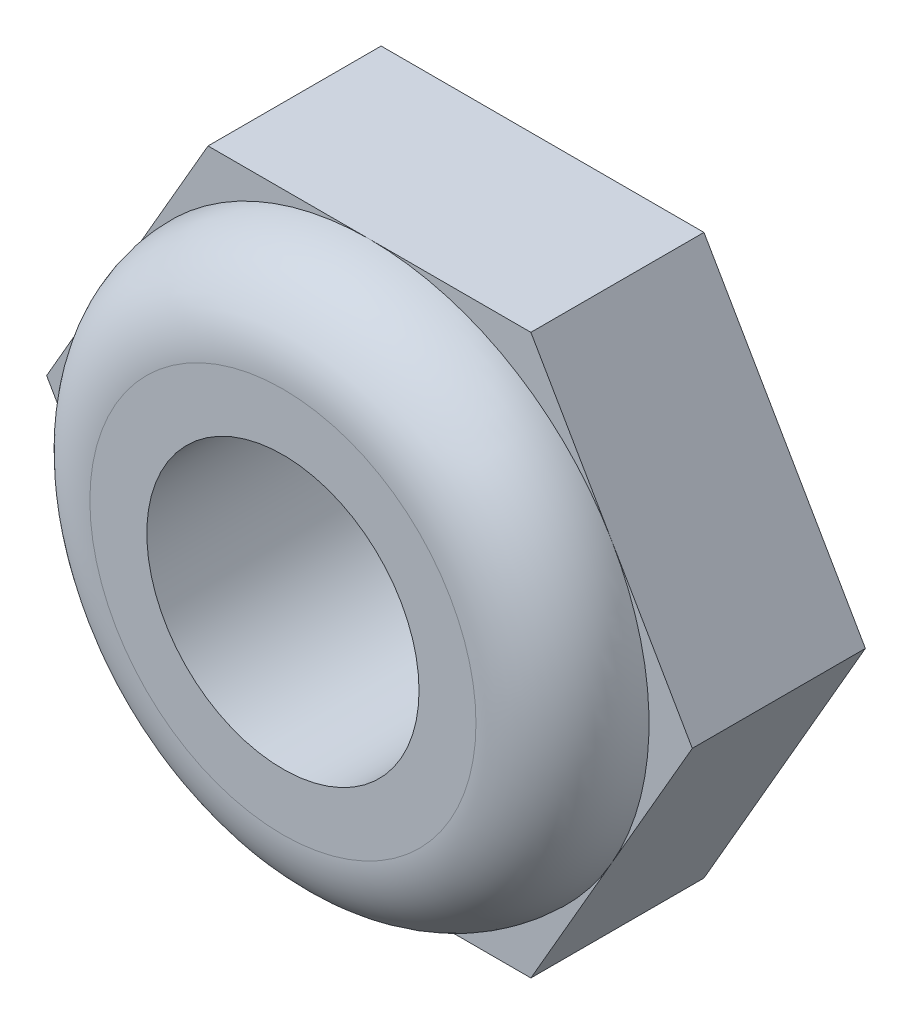
SolidWorks part; units mm, degrees
material "Alloy Steel"
ref_plane "Plane1" through (0, 0, 0) normal (0, 0, 1) x (1, 0, 0)
ref_plane "Plane2" through (0, 0, 0) normal (0, 1, 0) x (1, 0, 0)
ref_plane "Plane3" through (0, 0, 0) normal (1, 0, 0) x (0, 0, -1)
ref_axis "Axis1" through (-83.9706, 0, 0) along (1, 0, 0)
ref_axis "Axis2" through (0, 0, -0.258) along (0, 0, 1)
ref_axis "Axis3" through (0, 6.1119, 0) along (0, -1, 0)
sketch "Sketch1" plane through (0, 0, 0) normal (0, 0, 1) x (1, 0, 0)
  line L1 (3.2079, 5.5562) -> (-3.2079, 5.5562)
  line L2 (-3.2079, 5.5562) -> (-6.4158, 0)
  line L3 (-6.4158, 0) -> (-3.2079, -5.5563)
  line L4 (-3.2079, -5.5563) -> (3.2079, -5.5562)
  line L5 (3.2079, -5.5562) -> (6.4158, 0)
  line L6 (6.4158, 0) -> (3.2079, 5.5562)
  circle A0 centre (0, 0) radius 5.5562 construction
  circle A1 centre (0, 0) radius 2.7051
  dimension "D1" = 11.1125
  dimension "D2" = 5.4102
extrude "Boss-Extrude1" add sketch "Sketch1" along normal blind 5.1594
sketch "Sketch2" plane through (0, 0, 0) normal (1, 0, 0) x (0, 0, -1)
  line L0 (-3.4396, 5.5562) -> (-5.1594, 5.5562) construction
  line L1 (-5.1594, 5.5562) -> (0, 5.5562) construction
  line L2 (-5.1594, 5.5562) -> (-5.1594, 3.8365)
  line L3 (-5.1594, 0) -> (-5.1594, 5.5562) construction
  line L4 (-5.1594, 5.5562) -> (-5.1594, 8.3344)
  line L5 (-5.1594, 8.3344) -> (-3.4396, 8.3344)
  line L6 (-3.4396, 8.3344) -> (-3.4396, 5.5562)
  arc A0 (-5.1594, 3.8365) -> (-3.4396, 5.5562) centre (-3.4396, 3.8365) cw
  dimension "D1" = 1.7198
  dimension "D2" = 2.7781
revolve "Cut-Revolve2" cut sketch "Sketch2" angle 360 about axis through (0, 0, -0.258) along (0, 0, 1)
equation "\"w\"= 0.4375"
equation "\"h\"= 0.203125"
equation "\"tap\"= 0.213"
equation "\"D1@Sketch1\" = \"w\""
equation "\"D2@Sketch1\" = \"tap\""
equation "\"D1@Boss-Extrude1\" = \"h\""
equation "\"D1@Sketch2\" = \"h\" / 3"
equation "\"D2@Sketch2\" = \"w\" / 4"
